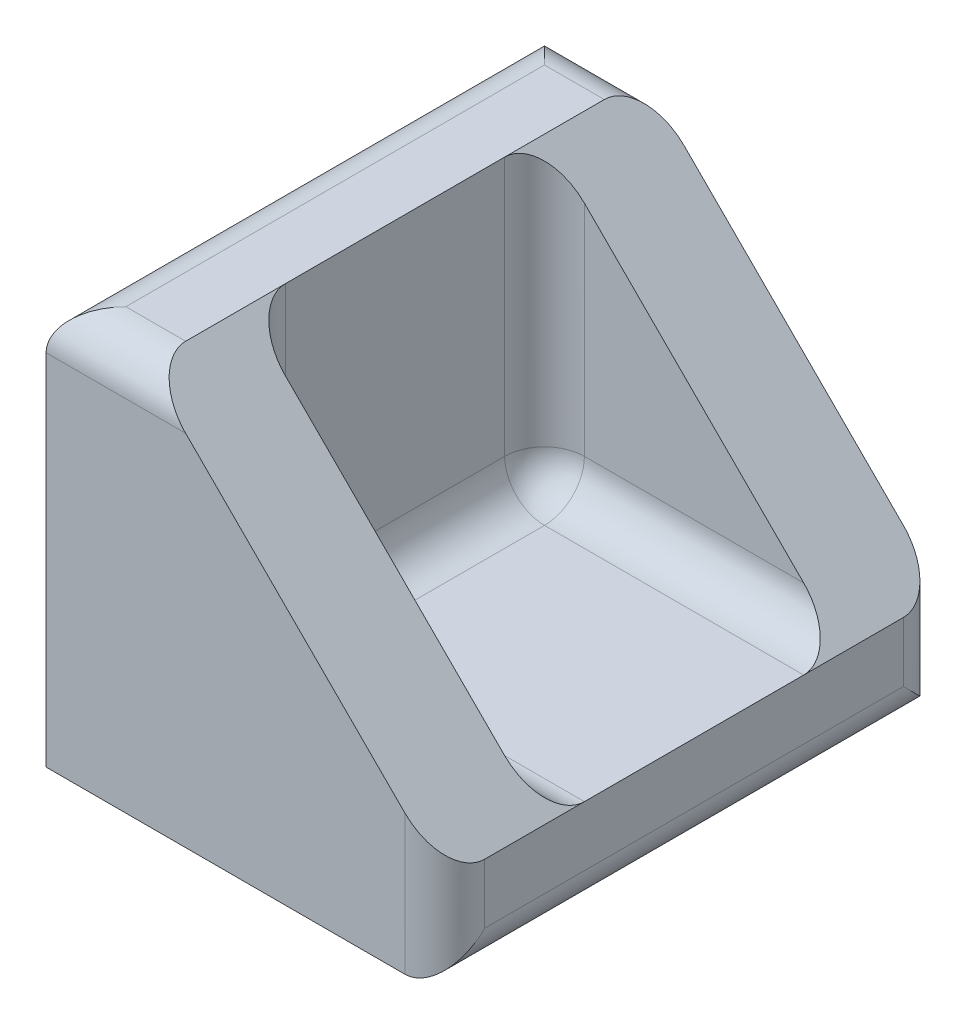
SolidWorks part; units mm, degrees
ref_plane "Front Plane" through (0, 0, 0) normal (0, 0, 1) x (1, 0, 0)
ref_plane "Top Plane" through (0, 0, 0) normal (0, 1, 0) x (1, 0, 0)
ref_plane "Right Plane" through (0, 0, 0) normal (1, 0, 0) x (0, 0, -1)
sketch "Sketch1" plane through (0, 0, 0) normal (0, 0, 1) x (1, 0, 0)
  line L0 (0, 0) -> (0, 20)
  line L1 (0, -55) -> (0, 55) construction
  line L2 (0, 20) -> (5, 20)
  line L5 (20, 5) -> (20, 0)
  line L6 (55, 0) -> (-55, 0) construction
  line L7 (20, 0) -> (0, 0)
  line L8 (5, 20) -> (20, 5)
  dimension "D1" = 5
  dimension "D2" = 5
  dimension "D3" = 20
  dimension "D4" = 20
extrude "Boss-Extrude2" add sketch "Sketch1" against normal blind 25
shell "Shell1" thickness 5 removed face at (12.5, 12.5, -12.5) removed face at (2.5, 20, -12.5) removed face at (20, 2.5, -12.5)
sketch "Sketch2" plane through (0, 5, 0) normal (0, 1, 0) x (1, 0, 0)
  line L0 (20, 12.5) -> (-3.555, 12.5) construction
  line L1 (20, 18) -> (20, 7) construction
  line L2 (0, -11) -> (0, 11) construction
  point P4 (12, 12.5)
  dimension "D1" = 12
sketch "Sketch3" plane through (5, 0, 0) normal (1, 0, 0) x (0, 0, -1)
  line L0 (12.5, 20) -> (12.5, -1.8484) construction
  line L1 (20, 20) -> (5, 20) construction
  line L2 (11, 0) -> (-11, 0) construction
  point P5 (12.5, 12)
  dimension "D1" = 12
fillet "Fillet1" radius 2 5 edges at (5, 5, -12.5) (5, 12.5, -20) (12.5, 5, -20) (5, 12.5, -5) (12.5, 5, -5)
fillet "Fillet3" radius 2 6 edges at (2.5, 20, -25) (20, 2.5, -25) (20, 2.5, 0) (2.5, 20, 0) (20, 0, -12.5) (0, 20, -12.5)
